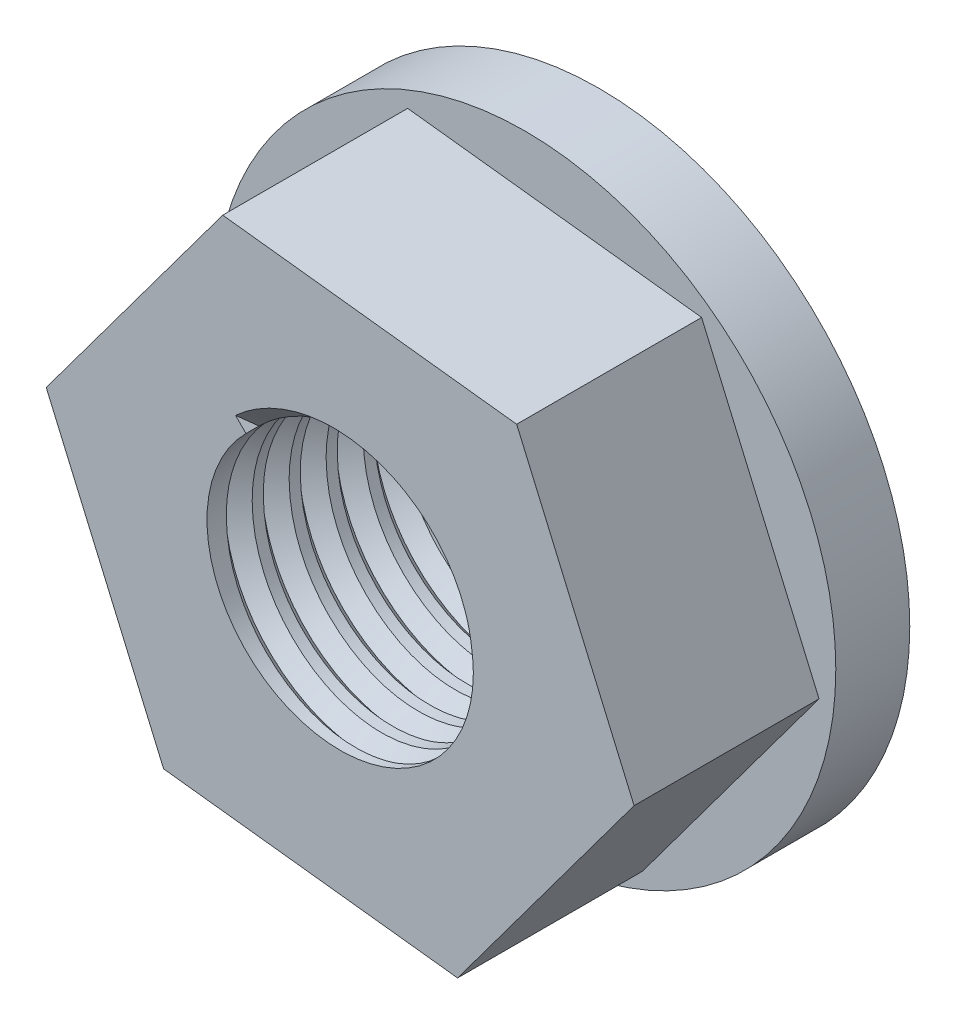
SolidWorks part; units mm, degrees
ref_plane "前视基准面" through (0, 0, 0) normal (0, 0, 1) x (1, 0, 0)
ref_plane "上视基准面" through (0, 0, 0) normal (0, 1, 0) x (1, 0, 0)
ref_plane "右视基准面" through (0, 0, 0) normal (1, 0, 0) x (0, 0, -1)
sketch "草图1" plane through (0, 0, 0) normal (0, 0, 1) x (1, 0, 0)
  circle A0 centre (0, 0) radius 8.4
  dimension "D1" = 16.8
extrude "凸台-拉伸1" add sketch "草图1" along normal blind 2
sketch "草图2" plane through (0, 0, 2) normal (0, 0, 1) x (1, 0, 0)
  line L1 (4.7721, 6.4209) -> (-3.1746, 7.3432)
  line L2 (-3.1746, 7.3432) -> (-7.9467, 0.9223)
  line L3 (-7.9467, 0.9223) -> (-4.7721, -6.4209)
  line L4 (-4.7721, -6.4209) -> (3.1746, -7.3432)
  line L5 (3.1746, -7.3432) -> (7.9467, -0.9223)
  line L6 (7.9467, -0.9223) -> (4.7721, 6.4209)
  circle A0 centre (0, 0) radius 8 construction
  dimension "D1" = 16
extrude "凸台-拉伸2" add sketch "草图2" along normal blind 5
sketch "草图3" plane through (0, 0, 7) normal (0, 0, 1) x (1, 0, 0)
  circle A0 centre (0, 0) radius 3.6
  dimension "D1" = 7.2
extrude "切除-拉伸1" cut sketch "草图3" against normal through all
sketch "草图8" plane through (0, 0, 7) normal (0, 0, 1) x (1, 0, 0)
  circle A0 centre (0, 0) radius 3.6
curve "螺旋线/涡状线2" pitch 1 height 6 radius 3.6 centre (0, 0, 7) axis (0, 0, -1) start towards (-0.7071, 0.7071, 0)
sketch "草图9" plane through (0, 0, 0) normal (1, 0, 0) x (0, 0, -1)
  line L0 (-7.225, 3.6) -> (-6.525, 3.6)
  line L1 (-7.225, 3.6) -> (-6.875, 4)
  line L2 (-6.875, 4) -> (-6.525, 3.6)
  line L3 (-6.875, 3.6) -> (-6.875, 4) construction
  dimension "D1" = 0.7
  dimension "D2" = 0.4
sweep "切除-扫描2" cut profiles "草图9" path "螺旋线/涡状线2"
